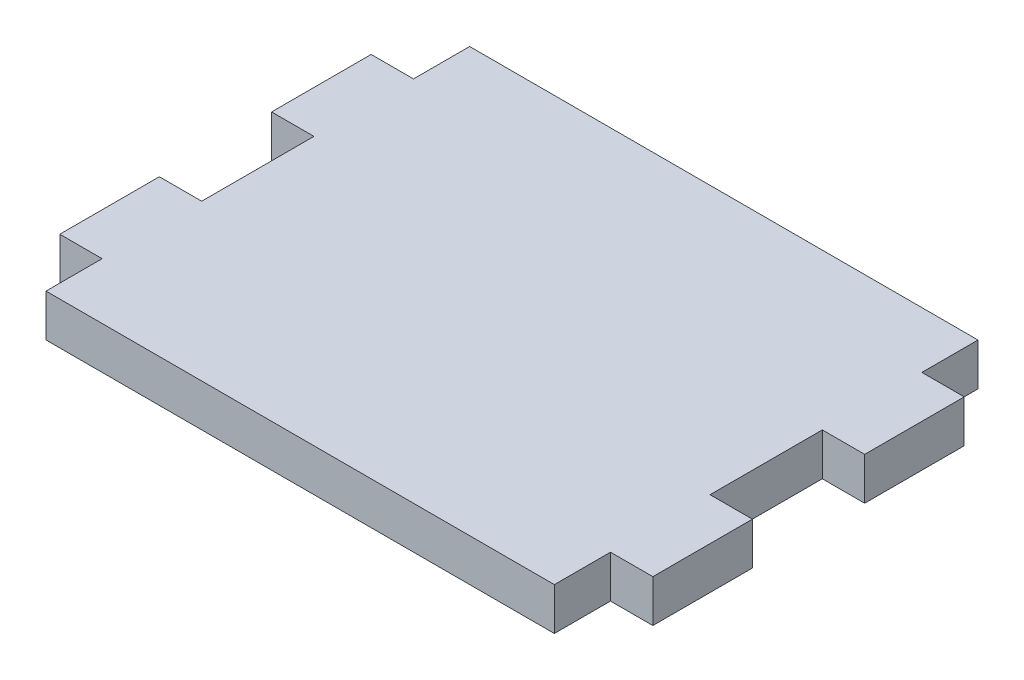
SolidWorks part; units mm, degrees
ref_plane "Front Plane" through (0, 0, 0) normal (0, 0, 1) x (1, 0, 0)
ref_plane "Top Plane" through (0, 0, 0) normal (0, 1, 0) x (1, 0, 0)
ref_plane "Right Plane" through (0, 0, 0) normal (1, 0, 0) x (0, 0, -1)
sketch "Sketch1" plane through (0, 0, 0) normal (0, 1, 0) x (1, 0, 0)
  line L0 (24, 40) -> (24, 0) construction
  line L1 (0, 0) -> (48, 0)
  line L2 (0, 0) -> (0, 5.3)
  line L3 (0, 40) -> (48, 40)
  line L4 (48, 0) -> (48, 5.3)
  line L5 (-4, 34.7) -> (0, 34.7)
  line L6 (-4, 34.7) -> (-4, 25.3)
  line L7 (-4, 25.3) -> (0, 25.3)
  line L9 (-4, 14.7) -> (0, 14.7)
  line L10 (-4, 14.7) -> (-4, 5.3)
  line L11 (-4, 5.3) -> (0, 5.3)
  line L14 (52, 5.3) -> (48, 5.3)
  line L15 (52, 14.7) -> (52, 5.3)
  line L16 (52, 14.7) -> (48, 14.7)
  line L18 (52, 25.3) -> (48, 25.3)
  line L19 (52, 34.7) -> (52, 25.3)
  line L20 (52, 34.7) -> (48, 34.7)
  line L21 (48, 0) -> (48, 5.3)
  line L22 (0, 34.7) -> (0, 40)
  line L23 (0, 14.7) -> (0, 25.3)
  line L24 (48, 34.7) -> (48, 40)
  line L25 (48, 34.7) -> (48, 40)
  line L26 (48, 14.7) -> (48, 25.3)
  line L27 (48, 14.7) -> (48, 25.3)
  dimension "D1" = 48
  dimension "D2" = 40
  dimension "D3" = 5.3
  dimension "D4" = 4
  dimension "D5" = 9.4
  dimension "D6" = 10.6
  dimension "D7" = 4
  dimension "D8" = 9.4
extrude "Boss-Extrude2" add sketch "Sketch1" along normal blind 4 contours L3 L0 L1 L4 L14 L15 L16 L26 L18 L19 L20 L24 | L0 L3 L22 L5 L6 L7 L23 L9 L10 L11 L2 L1 region at (37.017, 0, -20) region at (10.983, 0, -20)
